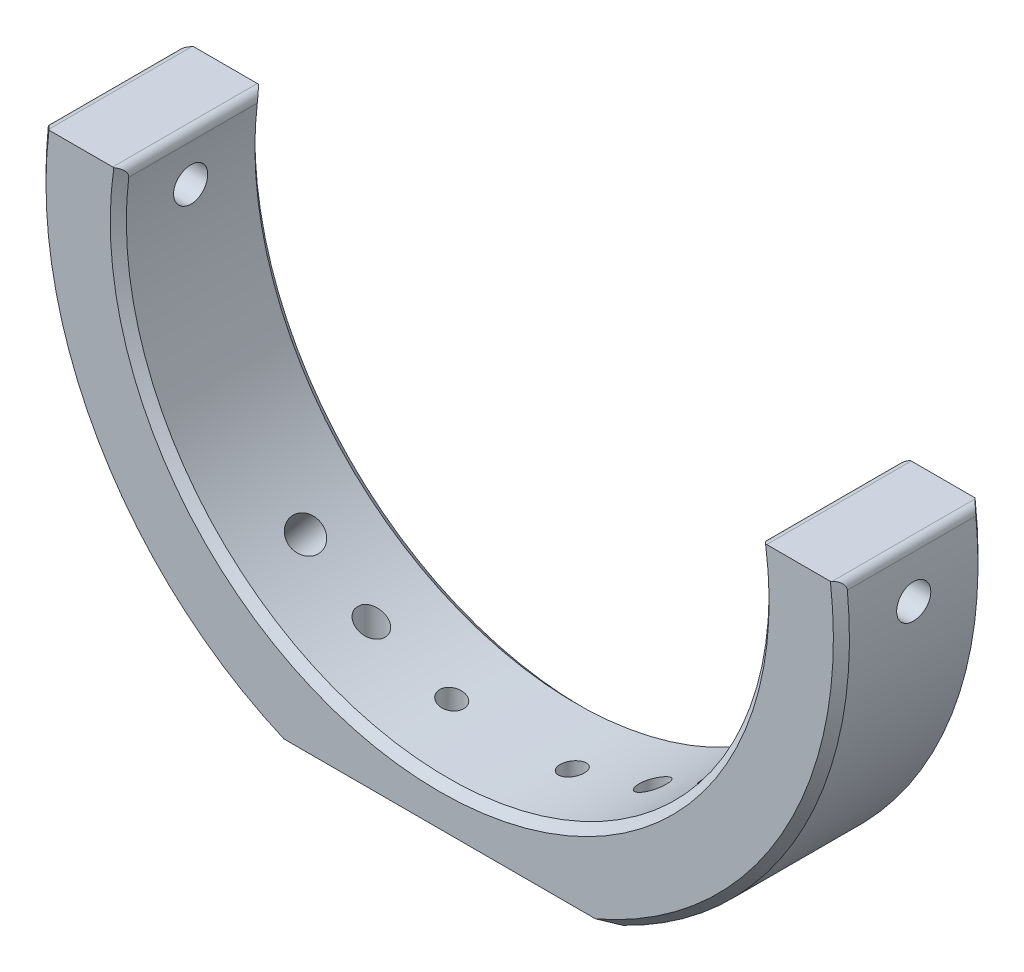
SolidWorks part; units mm, degrees
material "Q235A"
ref_plane "前视" through (0, 0, 0) normal (0, 0, 1) x (1, 0, 0)
ref_plane "上视" through (0, 0, 0) normal (0, 1, 0) x (1, 0, 0)
ref_plane "右视" through (0, 0, 0) normal (1, 0, 0) x (0, 0, -1)
sketch "草图1" plane through (0, 0, 0) normal (0, 0, 1) x (1, 0, 0)
  circle A0 centre (0, 0) radius 80
  circle A1 centre (0, 0) radius 100
  dimension "D1" = 160
  dimension "D2" = 200
extrude "凸台-拉伸1" add sketch "草图1" along normal blind 36
ref_axis "基准轴1" through (0, 0, 36) along (0, 0, -1)
chamfer "倒角1" distance 2 angle 45 4 edges at (80, 0, 0) (100, 0, 0) (80, 0, 36) (100, 0, 36)
sketch "草图4" plane through (0, 0, 36) normal (0, 0, 1) x (1, 0, 0)
  line L0 (-83.6879, -90) -> (117.5256, -90)
  line L1 (50, 0) -> (-50, 0) construction
  dimension "D1" = 90
extrude "切除-拉伸1" cut sketch "草图4" against normal through all and the other way through all flip side to cut
hole_wizard "大小mm 暗销孔1" positions "草图6" profile "草图5" hole size "Ø6.0" standard "GB"
sketch "草图6" plane through (0, -90, 0) normal (0, -1, 0) x (-1, 0, 0)
  line L0 (-38.7814, -36) -> (38.7814, -36) construction
  line L1 (0, 50) -> (0, -50) construction
  point P0 (15, -18)
  point P2 (-15, -18)
  dimension "D1" = 18
  dimension "D2" = 30
  dimension "D3" = 15
sketch "草图5" plane through (-15, -90, 18) normal (1, 0, 0) x (0, 0, -1)
  line L0 (0, 0) -> (0, 20.8026)
  line L1 (0, 20.8026) -> (3, 19)
  line L2 (3, 19) -> (3, 0)
  line L5 (3, 0) -> (0, 0)
  line L10 (0, 20.8026) -> (-3, 19) construction
  line L11 (0, -6.35) -> (0, 107.95) construction
  dimension "孔直径" = 6
  dimension "孔深度" = 19
  dimension "导头角度" = 118
hole_wizard "M8 螺纹孔1" positions "草图8" profile "草图7" tap size "M8" standard "GB"
sketch "草图8" plane through (0, -90, 0) normal (0, -1, 0) x (-1, 0, 0)
  line L0 (-38.7814, -36) -> (38.7814, -36) construction
  line L1 (0, 50) -> (0, -50) construction
  point P0 (35, -18)
  point P2 (-35, -18)
  dimension "D1" = 18
  dimension "D2" = 70
  dimension "D3" = 35
sketch "草图7" plane through (-35, -90, 18) normal (1, 0, 0) x (0, 0, -1)
  line L0 (0, 0) -> (0, 21.7929)
  line L1 (0, 21.7929) -> (3.4, 19.75)
  line L2 (3.4, 19.75) -> (3.4, 0)
  line L5 (3.4, 0) -> (0, 0)
  line L10 (0, 21.7929) -> (-3.4, 19.75) construction
  line L11 (0, -6.35) -> (0, 107.95) construction
  dimension "螺纹孔钻头直径" = 6.8
  dimension "螺纹孔钻头深度" = 19.75
  dimension "导头角度" = 118
cosmetic thread "孔螺蚊线2" parameters "D1"=16, "D2"=8
cosmetic thread "孔螺蚊线3" parameters "D1"=16, "D2"=8
ref_plane "基准面1" through (0, 0, 0) normal (0.866, -0.5, 0) x (0, 0, -1)
ref_plane "基准面2" through (-103.923, 60, 0) normal (0.866, -0.5, 0) x (0, 0, -1)
hole_wizard "M10 螺纹孔1" positions "草图11" profile "草图10" tap size "M10" standard "GB"
sketch "草图11" plane through (-103.923, 60, 0) normal (0.866, -0.5, 0) x (0, 0, -1)
  line L0 (0, -98) -> (0, 98) construction
  point P0 (-18, 0)
  dimension "D1" = 18
  dimension "D2" = 0
sketch "草图10" plane through (-103.923, 60, 18) normal (0, 0, 1) x (-0.5, -0.866, 0)
  line L0 (0, 0) -> (0, 42.5537)
  line L1 (0, 42.5537) -> (4.25, 40)
  line L2 (4.25, 40) -> (4.25, 0)
  line L5 (4.25, 0) -> (0, 0)
  line L10 (0, 42.5537) -> (-4.25, 40) construction
  line L11 (0, -6.35) -> (0, 107.95) construction
  dimension "螺纹孔钻头直径" = 8.5
  dimension "螺纹孔钻头深度" = 40
  dimension "导头角度" = 118
cosmetic thread "孔螺蚊线4" parameters "D1"=20, "D2"=10
pattern_circular "阵列(圆周)1" count 4 over 240 about axis through (0, 0, 36) along (0, 0, -1) of "M10 螺纹孔1" reverse direction yes
sketch "草图12" plane through (0, 0, 36) normal (0, 0, 1) x (1, 0, 0)
  line L1 (75, 16.0564) -> (-75, 16.0564)
  line L2 (75, 16.0564) -> (75, 113.6096)
  line L3 (75, 113.6096) -> (-75, 113.6096)
  line L4 (-75, 16.0564) -> (-75, 113.6096)
  line L5 (75, 16.0564) -> (-75, 113.6096) construction
  line L6 (75, 113.6096) -> (-75, 16.0564) construction
  point P0 (0, 64.833)
  dimension "D1" = 150
extrude "切除-拉伸2" cut sketch "草图12" against normal through all
fillet "圆角1" radius 5 2 edges at (-75, 66.1438, 18) (75, 66.1438, 18)
ref_plane "基准面3" through (130, 0, 0) normal (1, 0, 0) x (0, 0, -1)
hole_wizard "M10 螺纹孔2" positions "草图14" profile "草图13" tap size "M10" standard "GB" end condition through all
sketch "草图14" plane through (130, 0, 0) normal (1, 0, 0) x (0, 0, -1)
  line L0 (50, 0) -> (-50, 0) construction
  line L1 (-36, 0) -> (0, 0) construction
  point P0 (-18, 0)
  dimension "D1" = 18
sketch "草图13" plane through (130, 0, 18) normal (0, 1, 0) x (0, 0, -1)
  line L0 (0, 0) -> (0, 230)
  line L1 (0, 230) -> (4.25, 230)
  line L2 (4.25, 230) -> (4.25, 0)
  line L5 (4.25, 0) -> (0, 0)
  line L11 (0, -6.35) -> (0, 107.95) construction
  dimension "通孔螺纹孔钻头直径" = 8.5
  dimension "通孔螺纹孔钻头深度" = 230
cosmetic thread "孔螺蚊线5" parameters "D2"=10
sketch "草图15" plane through (0, 0, 36) normal (0, 0, 1) x (1, 0, 0)
  line L0 (50, 0) -> (-50, 0) construction
  line L1 (-129.0134, 75.6328) -> (106.9059, 75.6328)
  line L2 (-129.0134, 75.6328) -> (-129.0134, 12)
  line L3 (-129.0134, 12) -> (106.9059, 12)
  line L4 (106.9059, 75.6328) -> (106.9059, 12)
  dimension "D1" = 12
extrude "切除-拉伸3" cut sketch "草图15" against normal through all
fillet "圆角2" radius 2 4 edges at (99.2774, 12, 18) (79.0949, 12, 18) (-79.0949, 12, 18) (-99.2774, 12, 18)
